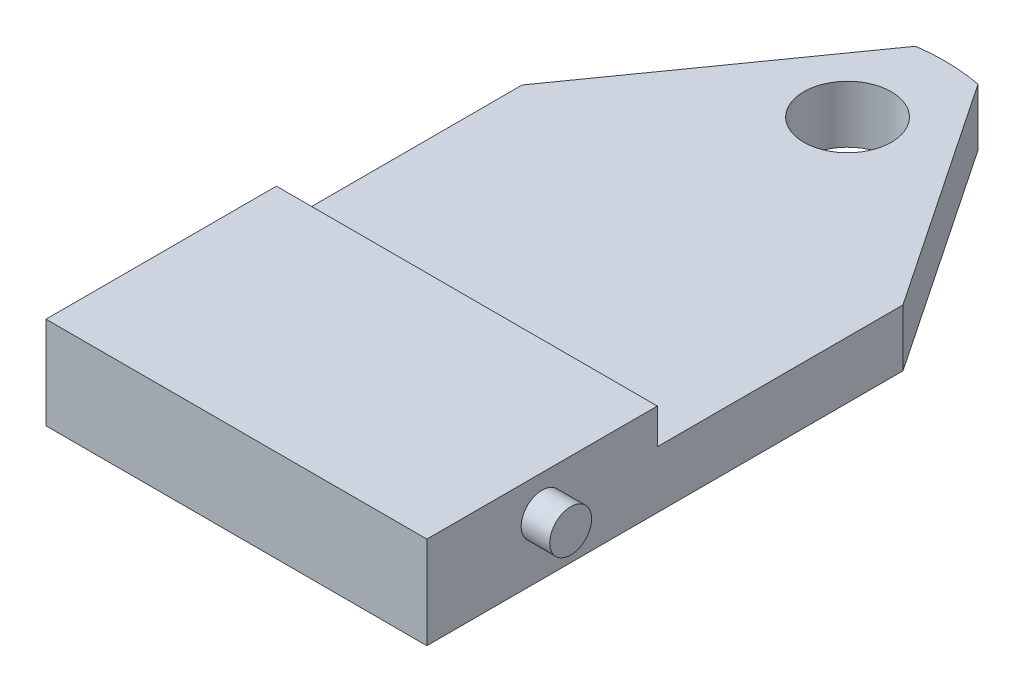
SolidWorks part; units mm, degrees
ref_plane "Front Plane" through (0, 0, 0) normal (0, 0, 1) x (1, 0, 0)
ref_plane "Top Plane" through (0, 0, 0) normal (0, 1, 0) x (1, 0, 0)
ref_plane "Right Plane" through (0, 0, 0) normal (1, 0, 0) x (0, 0, -1)
sketch "Sketch1" plane through (0, 0, 0) normal (0, 1, 0) x (1, 0, 0)
  line L2 (0, -15) -> (0, -40)
  line L3 (0, -40) -> (20, -40)
  line L4 (20, -15) -> (20, -40)
  line L11 (0, -15) -> (8.5665, -2.9111)
  line L12 (20, -15) -> (11.9329, -2.9947)
  circle A0 centre (10, -7.9118) radius 2.3
  arc A3 (8.5665, -2.9111) -> (11.9329, -2.9947) centre (10, -13.0066) cw
  dimension "D5" = 4.6
  dimension "D1" = 20
  dimension "D2" = 25
extrude "Boss-Extrude1" add sketch "Sketch1" along normal blind 3
sketch "Sketch2" plane through (20, 0, 0) normal (1, 0, 0) x (0, 0, -1)
  line L0 (-40, 3) -> (-40, 4.85)
  line L1 (-40, 4.85) -> (-27.9, 4.85)
  line L2 (-27.9, 4.85) -> (-27.9, 3)
  line L3 (-40, 3) -> (-15, 3) construction
  line L4 (-40, 3) -> (-27.9, 3)
  line L5 (-40, 0) -> (-15, 0) construction
  dimension "D1" = 12.1
  dimension "D2" = 4.85
extrude "Boss-Extrude3" add sketch "Sketch2" along normal up to surface from surface up to face at (20, 1.5, 27.5) starting at face at (0, 1.5, 27.5)
sketch "Sketch3" plane through (20, 0, 0) normal (1, 0, 0) x (0, 0, -1)
  circle A0 centre (-33.95, 2.95) radius 1.1
  dimension "D1" = 2.2
extrude "Boss-Extrude4" add sketch "Sketch3" along normal blind 1.5
